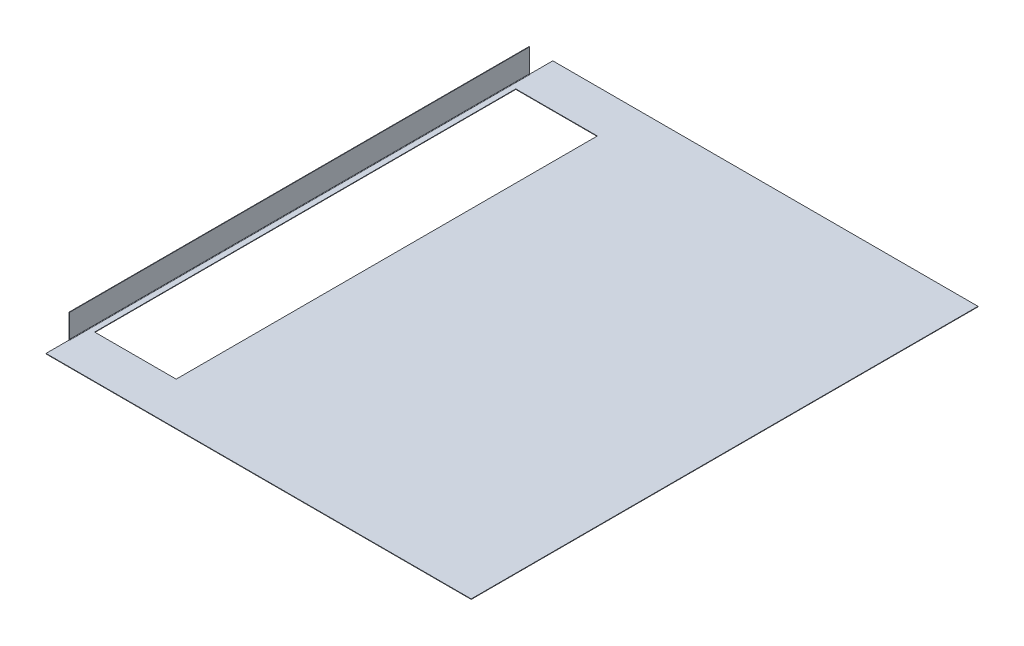
SolidWorks part; units mm, degrees
note: The reader was unsure of these and kept them because the rebuilt part matched: flange length of "Edge-Flange1".
material "AISI 1020 Steel, Cold Rolled"
ref_plane "Front Plane" through (0, 0, 0) normal (0, 0, 1) x (1, 0, 0)
ref_plane "Top Plane" through (0, 0, 0) normal (0, 1, 0) x (1, 0, 0)
ref_plane "Right Plane" through (0, 0, 0) normal (1, 0, 0) x (0, 0, -1)
sketch "Sketch1" plane through (0, 0, 0) normal (0, 1, 0) x (1, 0, 0)
  line L0 (-365, 0) -> (365, 0) construction
  line L1 (-365, -435) -> (365, -435)
  line L2 (-365, -435) -> (-365, 435)
  line L3 (-365, 435) -> (365, 435)
  line L4 (365, -435) -> (365, 435)
  line L5 (-365, -435) -> (365, 435) construction
  line L6 (-365, 435) -> (365, -435) construction
  line L8 (-355, -361.5) -> (-215, -361.5)
  line L9 (-355, -361.5) -> (-355, 361.5)
  line L10 (-355, 361.5) -> (-215, 361.5)
  line L11 (-215, -361.5) -> (-215, 361.5)
  line L12 (-355, -361.5) -> (-215, 361.5) construction
  line L13 (-355, 361.5) -> (-215, -361.5) construction
  point P0 (0, 0)
  point P8 (-285, 0)
  dimension "D1" = 730
  dimension "D2" = 870
  dimension "D3" = 723
  dimension "D4" = 10
  dimension "D5" = 140
sheet metal parameters "Sheet-Metal1" thickness 0.8 parameters "D1"=0.8
base flange "Base-Flange1" sketch "Sketch1" thickness 0.8 reverse thickness direction no parameters "D1"=0.8
edge flange "Edge-Flange1" sketch "Sketch5" flange angle 90 flange length 41.6 flange position material outside bend radius 0.8 thickness 0.8 relief none parameters "D6"=10
sketch "Sketch5" plane through (-365, 0, 0) normal (-1, 0, 0) x (0, 0, 1)
  line L0 (-435, 0) -> (435, 0) construction
  line L1 (-395, 0) -> (395, 0)
  line L2 (-395, 0) -> (-395, 40.8)
  line L3 (-395, 40.8) -> (395, 40.8)
  line L4 (395, 40.8) -> (395, 0)
  dimension "D1" = 40
  dimension "D2" = 40
bend "EdgeBend1" bend radius 0.8 bend angle 90 parameters "D5"=1
flat pattern "Flat-Pattern1" [suppressed]
sketch "Bend-Lines1" plane through (0, 0, 0) normal (0, 1, 0) x (-1, 0, 0)
  line L0 (433.1111, -454.25) -> (433.1111, 454.25) construction
  line L1 (433.1111, -454.25) -> (433.1111, 454.25) construction
bend of the flat pattern "Flatten-<EdgeBend1>1"
